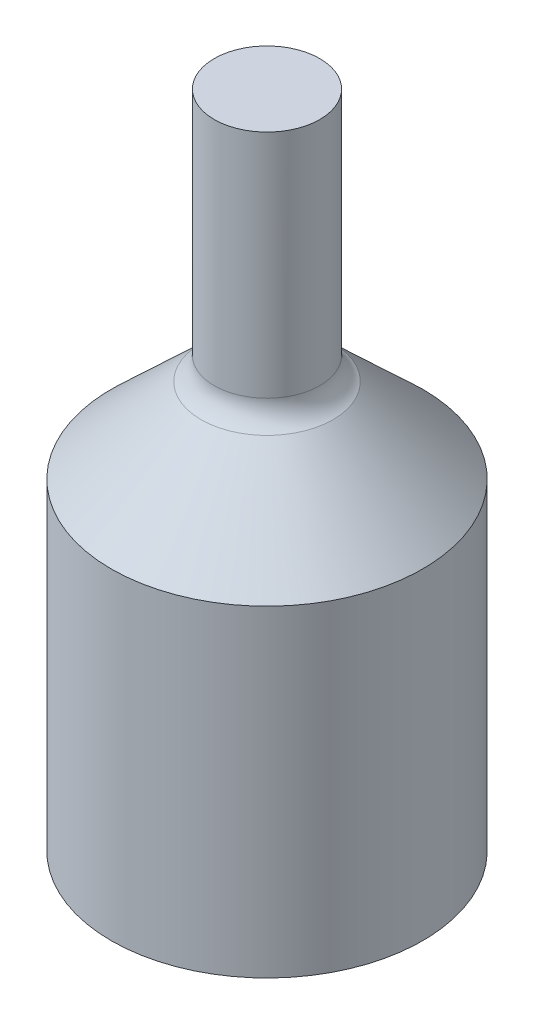
SolidWorks part; units mm, degrees
ref_plane "Front Plane" through (0, 0, 0) normal (0, 0, 1) x (1, 0, 0)
ref_plane "Top Plane" through (0, 0, 0) normal (0, 1, 0) x (1, 0, 0)
ref_plane "Right Plane" through (0, 0, 0) normal (1, 0, 0) x (0, 0, -1)
sketch "Sketch1" plane through (0, 0, 0) normal (0, 1, 0) x (1, 0, 0)
  circle A0 centre (0, 0) radius 2.95
  dimension "D1" = 5.9
extrude "Boss-Extrude1" add sketch "Sketch1" along normal blind 7.7
ref_axis "Axis1" through (0, 7.7, 0) along (0, -1, 0)
sketch "Sketch2" plane through (0, 0, 0) normal (0, 0, 1) x (1, 0, 0)
  line L0 (-2.95, 6.1) -> (-1.25, 7.7)
  line L1 (-2.95, 7.7) -> (-2.95, 0) construction
  line L2 (2.95, 7.7) -> (-2.95, 7.7) construction
  line L3 (-1.25, 7.7) -> (-2.95, 7.7)
  line L4 (-2.95, 7.7) -> (-2.95, 6.1)
  dimension "D1" = 1.7
  dimension "D2" = 1.6
revolve "Cut-Revolve1" cut sketch "Sketch2" angle 360 about axis through (0, 7.7, 0) along (0, -1, 0)
sketch "Sketch3" plane through (0, 7.7, 0) normal (0, 1, 0) x (1, 0, 0)
  circle A0 centre (0, 0) radius 1
  dimension "D1" = 2
extrude "Boss-Extrude2" add sketch "Sketch3" along normal blind 4.8
fillet "Fillet1" radius 0.5 1 edges at (0, 7.7, 1)
